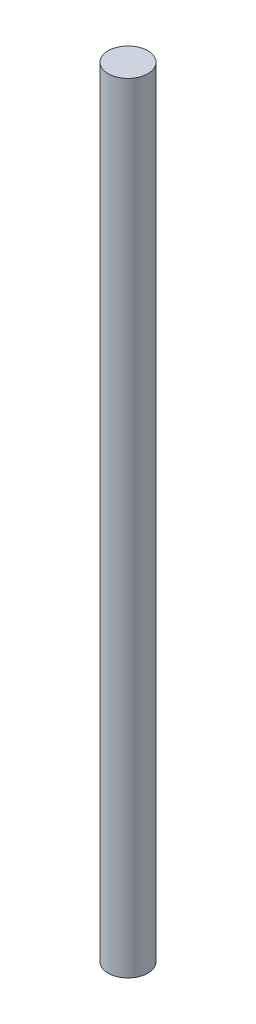
SolidWorks part; units mm, degrees
ref_plane "Front Plane" through (0, 0, 0) normal (0, 0, 1) x (1, 0, 0)
ref_plane "Top Plane" through (0, 0, 0) normal (0, 1, 0) x (1, 0, 0)
ref_plane "Right Plane" through (0, 0, 0) normal (1, 0, 0) x (0, 0, -1)
sketch "Sketch1" plane through (0, 0, 0) normal (0, 1, 0) x (1, 0, 0)
  circle A0 centre (0, 0) radius 3.175
  dimension "D1" = 6.35
extrude "Boss-Extrude1" add sketch "Sketch1" along normal blind 124.46
